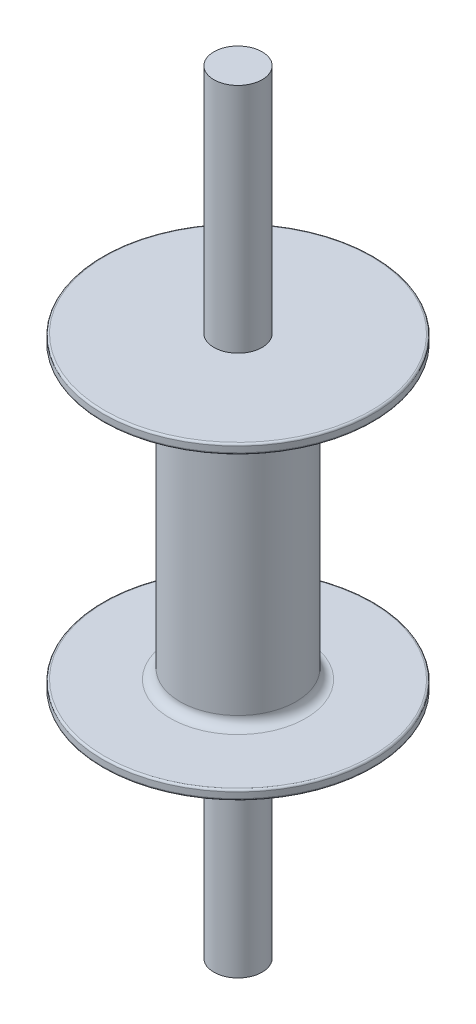
SolidWorks part; units mm, degrees
ref_plane "Front Plane" through (0, 0, 0) normal (0, 0, 1) x (1, 0, 0)
ref_plane "Top Plane" through (0, 0, 0) normal (0, 1, 0) x (1, 0, 0)
ref_plane "Right Plane" through (0, 0, 0) normal (1, 0, 0) x (0, 0, -1)
sketch "Sketch1" plane through (0, 0, 0) normal (0, 1, 0) x (1, 0, 0)
  circle A1 centre (0, 0) radius 60
  dimension "D2" = 120
extrude "Boss-Extrude1" add sketch "Sketch1" along normal blind 150 and the other way blind 150
sketch "Sketch2" plane through (0, 150, 0) normal (0, 1, 0) x (1, 0, 0)
  circle A0 centre (0, 0) radius 140
  dimension "D1" = 280
extrude "Boss-Extrude2" add sketch "Sketch2" along normal blind 10
mirror "Mirror1" about plane through (0, 0, 0) normal (0, 1, 0) of "Boss-Extrude2"
sketch "Sketch3" plane through (0, 0, 0) normal (0, 1, 0) x (1, 0, 0)
  circle A0 centre (0, 0) radius 25
  dimension "D1" = 50
extrude "Boss-Extrude3" add sketch "Sketch3" along normal blind 400 and the other way blind 400
fillet "Fillet1" radius 10 1 edges at (0, 150, 60)
fillet "Fillet2" radius 10 1 edges at (0, -150, -60)
fillet "Fillet3" radius 2 1 edges at (0, 150, 140)
fillet "Fillet4" radius 2 1 edges at (0, -150, 140)
fillet "Fillet5" radius 2 1 edges at (0, 160, 140)
fillet "Fillet6" radius 2 1 edges at (0, -160, 140)
